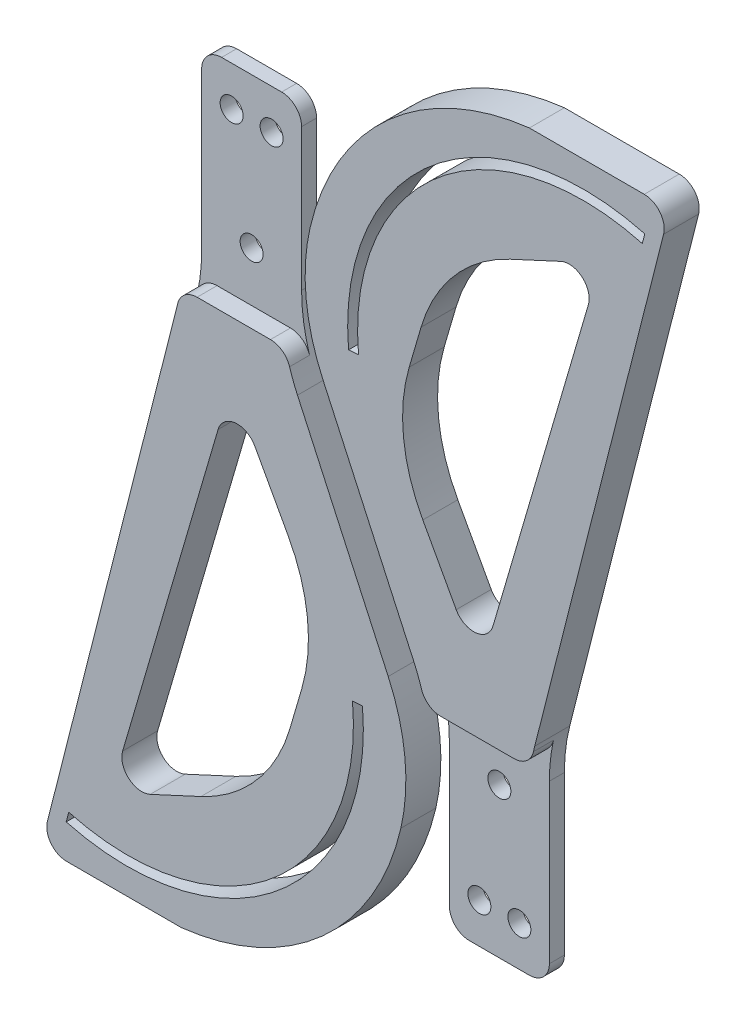
SolidWorks part; units mm, degrees
ref_plane "Front Plane" through (0, 0, 0) normal (0, 0, 1) x (1, 0, 0)
ref_plane "Top Plane" through (0, 0, 0) normal (0, 1, 0) x (1, 0, 0)
ref_plane "Right Plane" through (0, 0, 0) normal (1, 0, 0) x (0, 0, -1)
sketch "Sketch1" plane through (0, 0, 0) normal (0, 0, 1) x (1, 0, 0)
  line L0 (-10, 0) -> (-10, 40)
  line L1 (24.2736, 134.5199) -> (0, 51.5556)
  line L2 (32.5815, 142.0692) -> (33.0979, 144.0013)
  line L3 (-10, 0) -> (10, 0)
  line L4 (-26.1752, 94.2653) -> (-24.1827, 94.4383)
  line L5 (10, 150.7971) -> (38.123, 150.7971)
  line L6 (38.123, 150.7971) -> (10, 40)
  line L7 (10, 40) -> (10, 0)
  line L8 (-34.8351, 94.2653) -> (-10, 40)
  line L9 (0, 51.5556) -> (-17.8773, 84.2205)
  line L10 (-17.8773, 84.2205) -> (-7.4576, 119.8337)
  line L11 (-7.4576, 119.8337) -> (24.2736, 134.5199)
  circle A0 centre (0, 30) radius 2.3
  circle A1 centre (4, 8) radius 2.3
  circle A2 centre (-4, 8) radius 2.3
  arc A3 (33.0979, 144.0013) -> (-26.1752, 94.2653) centre (20.8976, 98.3536) ccw
  arc A4 (32.5815, 142.0692) -> (-24.1827, 94.4383) centre (20.7611, 98.5163) ccw
  arc A5 (10, 150.7971) -> (-34.8351, 94.2653) centre (15.8484, 100.1137) ccw
  point P0 (-10, 0)
  point P1 (10, 0)
  point P2 (4, 8)
  point P3 (-4, 8)
  point P4 (10, 40)
  point P5 (-10, 40)
  point P6 (0, 30)
  point P23 (32.5815, 142.0692)
  point P24 (-24.1827, 94.4383)
extrude "Extrude1" add sketch "Sketch1" along normal blind 7
fillet "Fillet1" radius 39 1 edges at (-34.8351, 94.2653, 3.5)
fillet "Fillet2" radius 33 2 edges at (-17.8773, 84.2205, 3.5) (-7.4576, 119.8337, 3.5)
fillet "Fillet3" radius 4 5 edges at (-10, 0, 3.5) (10, 0, 3.5) (0, 51.5556, 3.5) (24.2736, 134.5199, 3.5) (38.123, 150.7971, 3.5)
fillet "Fillet4" radius 35 2 edges at (-10, 40, 3.5) (10, 40, 3.5)
sketch "Sketch2" plane through (0, 0, 7) normal (0, 0, 1) x (1, 0, 0)
  line L1 (16.3558, 0) -> (-16.5899, 0)
  line L2 (16.3558, 0) -> (16.3558, 40)
  line L3 (16.3558, 40) -> (-16.5899, 40)
  line L4 (-16.5899, 0) -> (-16.5899, 40)
extrude "Cut-Extrude1" cut sketch "Sketch2" against normal blind 4
fillet "Fillet5" radius 4 2 edges at (-10.8415, 40, 5) (10.2742, 40, 5)
sketch "Sketch3" plane through (0, 0, 0) normal (0, 0, 1) x (1, 0, 0)
  circle A0 centre (-24.7818, 64.1218) radius 1.1999
extrude "Extrude2" add sketch "Sketch3" along normal blind 0.1
ref_axis "Axis1" through (-24.7818, 64.1218, 0.1) along (0, 0, -1)
pattern_circular "CirPattern1" count 2 over 360 about axis through (-24.7818, 64.1218, 0.1) along (0, 0, -1) of bodies 102
